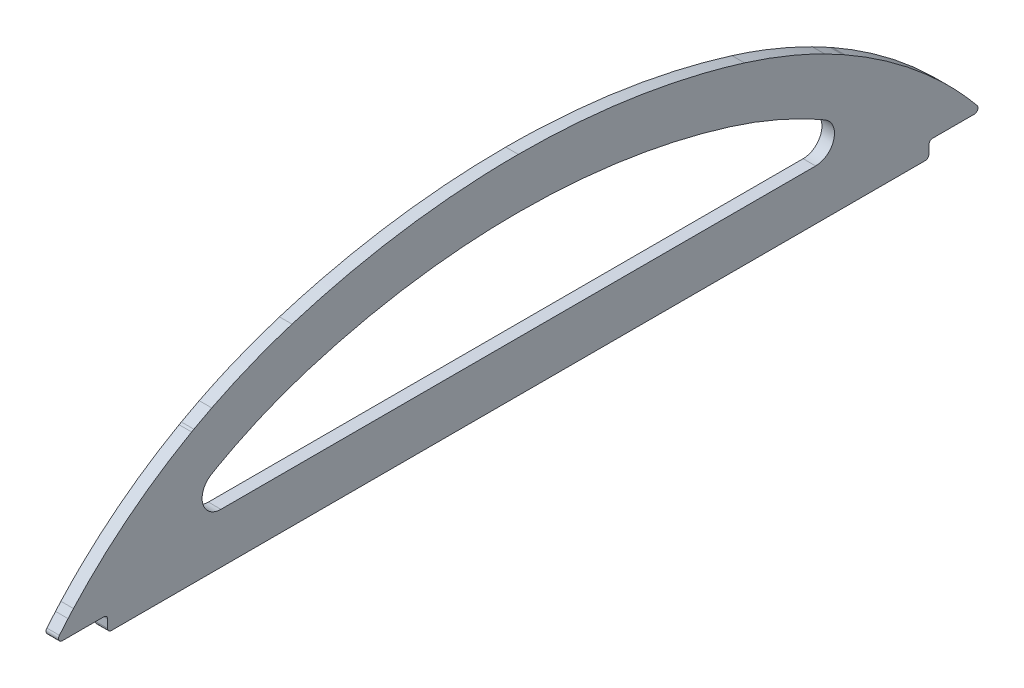
SolidWorks part; units mm, degrees
ref_plane "Front Plane" through (0, 0, 0) normal (0, 0, 1) x (1, 0, 0)
ref_plane "Top Plane" through (0, 0, 0) normal (0, 1, 0) x (1, 0, 0)
ref_plane "Right Plane" through (0, 0, 0) normal (1, 0, 0) x (0, 0, -1)
sketch "Sketch1" plane through (0, 0, 0) normal (1, 0, 0) x (0, 0, -1)
  line L0 (-96.2946, 5.9495) -> (96.2944, 5.9495)
  line L1 (-83.0866, 5.9495) -> (-83.0866, 9.1245)
  line L2 (-83.0866, 9.1245) -> (-93.8548, 9.1245)
  line L3 (83.0869, 5.9495) -> (83.0869, 9.1245)
  line L4 (83.0869, 9.1245) -> (93.8551, 9.1245)
  line L5 (72.5185, 16.1095) -> (-72.5187, 16.1095)
  spline S0 degree 3 poles (96.2944, 5.9495) (95.3162, 7.2776) (94.3159, 8.5664) (93.296, 9.8158) knots 0.775734 0.775734 0.775734 0.775734 1 1 1 1
  spline S1 degree 3 poles (93.296, 9.8158) (92.5735, 10.7008) (91.8374, 11.5701) (91.0886, 12.4237) knots 0 0 0 0 1 1 1 1
  spline S2 degree 3 poles (91.0886, 12.4237) (90.7324, 12.8297) (90.3692, 13.2365) (89.9993, 13.6442) knots 0 0 0 0 0.999999 0.999999 0.999999 0.999999
  spline S3 degree 3 poles (89.9993, 13.6442) (88.2637, 15.5574) (86.4569, 17.3838) (83.6563, 19.9929) (81.8777, 21.5829) (79.9594, 23.172) (79.0037, 23.9336) (78.8802, 24.0316) (78.8501, 24.0555) (74.7664, 27.2888) (70.4984, 30.1374) (66.0898, 32.6255) knots 0 0 0 0 0.25 0.25 0.375 0.484375 0.496094 0.496094 0.5 0.5 1 1 1 1
  spline S4 degree 3 poles (65.6328, 32.882) (64.439, 33.5479) (63.233, 34.1886) (62.0163, 34.8041) knots 0 0 0 0 0.18827 0.18827 0.18827 0.18827
  spline S5 degree 3 poles (66.0898, 32.6255) (65.9377, 32.7114) (65.7854, 32.7968) (65.6328, 32.882) knots 0 0 0 0 0.999999 0.999999 0.999999 0.999999
  spline S6 degree 3 poles (-96.2946, 5.9495) (-96.0496, 6.2797) (-95.5608, 6.9384) (-94.8141, 7.9117) (-94.0613, 8.8716) (-93.5507, 9.5017) (-93.2961, 9.8158) knots 0 0 0 0 0.252116 0.502813 0.752104 1 1 1 1
  spline S7 degree 3 poles (-93.2961, 9.8158) (-93.0545, 10.1097) (-92.5718, 10.6967) (-91.8358, 11.566) (-91.3376, 12.138) (-91.0888, 12.4237) knots 0 0 0 0 0.334016 0.667347 1 1 1 1
  spline S8 degree 3 poles (-91.0888, 12.4237) (-90.9093, 12.6273) (-90.5488, 13.0364) (-90.1831, 13.441) (-89.9995, 13.6442) knots 0 0 0 0 0.497638 1 1 1 1
  spline S9 degree 3 poles (-89.9995, 13.6442) (-89.7316, 13.9372) (-89.1963, 14.5227) (-88.3797, 15.3867) (-87.5543, 16.2391) (-86.7192, 17.0789) (-85.875, 17.9064) (-84.4559, 19.2626) (-82.7167, 20.8423) (-80.9328, 22.3643) (-79.7295, 23.3532) (-78.4521, 24.3773) (-76.7841, 25.6621) (-74.7061, 27.1763) (-72.5966, 28.6308) (-70.4569, 30.0242) (-68.2917, 31.3616) (-66.8231, 32.2047) (-66.09, 32.6255) knots 0 0 0 0 0.03885 0.077625 0.116327 0.154956 0.193513 0.232 0.347035 0.423377 0.461445 0.499444 0.583588 0.667444 0.751013 0.834295 0.917291 1 1 1 1
  spline S10 degree 3 poles (-66.09, 32.6255) (-65.9379, 32.7114) (-65.7855, 32.7968) (-65.6329, 32.882) knots 0 0 0 0 1 1 1 1
  spline S11 degree 3 poles (-65.6329, 32.882) (-65.3341, 33.0475) (-64.7366, 33.3786) (-63.8342, 33.8632) (-62.9282, 34.3396) (-62.3203, 34.6493) (-62.0164, 34.8041) knots 0 0 0 0 0.250232 0.500309 0.750231 1 1 1 1
  spline S12 degree 3 poles (-62.0164, 34.8041) (-61.1402, 35.2383) (-59.3888, 36.106) (-56.7181, 37.3111) (-54.0212, 38.445) (-51.2966, 39.499) (-48.5499, 40.4818) (-46.6986, 41.0723) (-45.7736, 41.3673) knots 0 0 0 0 0.167265 0.334295 0.501086 0.667635 0.83394 1 1 1 1
  spline S13 degree 3 poles (-45.7736, 41.3673) (-44.5402, 41.7394) (-42.0735, 42.4836) (-38.3385, 43.4787) (-34.5811, 44.385) (-30.8008, 45.1942) (-27.0006, 45.9085) (-23.1821, 46.5276) (-19.3476, 47.0516) (-15.4988, 47.4802) (-11.6376, 47.8142) (-7.7659, 48.0509) (-3.8856, 48.199) (-1.2957, 48.2167) (0, 48.2256) knots 0 0 0 0 0.083186 0.16637 0.249558 0.332759 0.415981 0.499234 0.582527 0.665873 0.749281 0.832764 0.916333 1 1 1 1
  spline S14 degree 3 poles (0, 48.2256) (1.2957, 48.2167) (3.8856, 48.199) (7.7659, 48.0509) (11.6376, 47.8142) (15.4987, 47.4802) (19.3475, 47.0516) (23.1821, 46.5276) (27.0005, 45.9085) (30.8007, 45.1941) (34.581, 44.385) (38.3384, 43.4787) (42.0734, 42.4836) (44.5401, 41.7394) (45.7734, 41.3673) knots 0 0 0 0 0.083667 0.167236 0.250719 0.334127 0.417473 0.500766 0.584019 0.667241 0.750442 0.83363 0.916814 1 1 1 1
  spline S15 degree 3 poles (45.7734, 41.3673) (46.6984, 41.0723) (48.5497, 40.4818) (51.2965, 39.499) (54.0211, 38.445) (56.718, 37.3111) (59.3887, 36.106) (61.14, 35.2383) (62.0163, 34.8041) knots 0 0 0 0 0.16606 0.332365 0.498914 0.665705 0.832735 1 1 1 1
  spline S26 degree 3 poles (-82.5005, 6.7892) (-82.2976, 7.0111) (-81.8761, 7.4722) (-81.3314, 8.054) (-80.7305, 8.6819) (-79.5477, 9.893) (-77.1002, 12.2713) (-74.3071, 14.695) (-71.6232, 16.8205) (-69.5673, 18.3671) (-67.4583, 19.8435) (-65.545, 21.1) (-64.3225, 21.8715) (-63.3625, 22.4571) (-62.6461, 22.8824) (-61.883, 23.3255) (-61.3348, 23.6402) (-61.0655, 23.7948) knots 0 0 0 0 0.03121 0.062421 0.093631 0.124842 0.249684 0.467905 0.530326 0.624209 0.749051 0.811472 0.873893 0.905103 0.936313 0.967524 0.998734 0.998734 0.998734 0.998734
  spline S27 degree 3 poles (-61.0655, 23.7948) (-61.0347, 23.8122) (-60.9732, 23.8468) (-60.8808, 23.8987) (-60.7883, 23.9505) (-60.7265, 23.9851) (-60.6956, 24.0023) knots 0.077726 0.077726 0.077726 0.077726 0.300433 0.523141 0.745848 0.968556 0.968556 0.968556 0.968556
  spline S28 degree 3 poles (-60.6956, 24.0023) (-60.5539, 24.0808) (-60.2624, 24.2422) (-59.7437, 24.5274) (-59.085, 24.8812) (-58.417, 25.2328) (-57.894, 25.5017) (-57.5985, 25.6524) (-57.4549, 25.7255) knots 0.003841 0.003841 0.003841 0.003841 0.126618 0.249395 0.494948 0.740501 0.863278 0.986054 0.986054 0.986054 0.986054
  spline S29 degree 3 poles (-57.4549, 25.7255) (-57.1384, 25.8823) (-56.4946, 26.2012) (-55.5903, 26.643) (-54.7306, 27.0521) (-53.5649, 27.5878) (-52.0522, 28.2524) (-50.2407, 29.007) (-48.4136, 29.722) (-46.8612, 30.2954) (-45.6454, 30.7221) (-44.7404, 31.0266) (-43.7827, 31.3379) (-43.0988, 31.5562) (-42.7624, 31.6635) knots 0.003251 0.003251 0.003251 0.003251 0.065263 0.127274 0.189286 0.251298 0.375321 0.499344 0.623367 0.74739 0.809401 0.871413 0.933424 0.995436 0.995436 0.995436 0.995436
  spline S30 degree 3 poles (-42.7624, 31.6635) (-42.3088, 31.8003) (-41.3911, 32.077) (-40.0755, 32.4668) (-38.8039, 32.8301) (-37.0888, 33.2976) (-34.8955, 33.8597) (-31.3915, 34.6916) (-26.9816, 35.6043) (-21.6471, 36.502) (-16.2801, 37.1998) (-11.79, 37.616) (-8.1875, 37.8477) (-5.921, 37.9544) (-4.1384, 38.0121) (-2.8096, 38.0395) (-1.4333, 38.0554) (-0.4743, 38.0621) (0, 38.0653) knots 0.001722 0.001722 0.001722 0.001722 0.032872 0.064021 0.095171 0.12632 0.188619 0.250918 0.375516 0.500113 0.624711 0.749309 0.811608 0.873907 0.905056 0.936206 0.967355 0.998505 0.998505 0.998505 0.998505
  spline S31 degree 3 poles (0, 38.0653) (0.4743, 38.0621) (1.4333, 38.0554) (2.8096, 38.0395) (4.1384, 38.0121) (5.9209, 37.9544) (8.1875, 37.8477) (11.7899, 37.616) (16.28, 37.1998) (21.6471, 36.502) (26.9815, 35.6043) (31.3914, 34.6916) (34.8954, 33.8597) (37.0887, 33.2976) (38.8037, 32.8301) (40.0754, 32.4668) (41.3909, 32.077) (42.3086, 31.8003) (42.7622, 31.6635) knots 0.001495 0.001495 0.001495 0.001495 0.032645 0.063794 0.094944 0.126093 0.188392 0.250691 0.375289 0.499887 0.624484 0.749082 0.811381 0.87368 0.90483 0.935979 0.967128 0.998278 0.998278 0.998278 0.998278
  spline S32 degree 3 poles (42.7622, 31.6635) (43.0989, 31.5561) (43.7833, 31.3376) (44.7417, 31.0261) (45.6473, 30.7213) (46.8641, 30.2943) (48.4178, 29.7204) (50.2461, 29.0048) (52.0591, 28.2494) (53.5729, 27.5841) (54.7391, 27.0481) (55.5998, 26.6384) (56.5052, 26.1958) (57.1498, 25.8766) (57.4668, 25.7195) knots 0.004564 0.004564 0.004564 0.004564 0.066624 0.128683 0.190743 0.252802 0.376922 0.501041 0.62516 0.749279 0.811339 0.873398 0.935458 0.997518 0.997518 0.997518 0.997518
  spline S33 degree 3 poles (57.4668, 25.7195) (57.7376, 25.5824) (58.2778, 25.3055) (59.0839, 24.882) (59.8859, 24.4504) (60.4176, 24.1573) (60.6828, 24.0094) knots 0.000025 0.000025 0.000025 0.000025 0.046559 0.093093 0.139626 0.18616 0.18616 0.18616 0.18616
  spline S34 degree 3 poles (60.6828, 24.0094) (60.7174, 23.9901) (60.7866, 23.9514) (60.8902, 23.8934) (60.9936, 23.8353) (61.0624, 23.7965) (61.0968, 23.7771) knots 0.001594 0.001594 0.001594 0.001594 0.250933 0.500272 0.749611 0.998951 0.998951 0.998951 0.998951
  spline S35 degree 3 poles (61.0968, 23.7771) (63.0869, 22.6538) (66.004, 20.858) (69.6507, 18.3105) (71.617, 16.8241) (72.9748, 15.7485) (73.9468, 14.9589) (75.5712, 13.5924) (78.5305, 10.9467) (80.9502, 8.4997) (82.4841, 6.8087) knots 0 0 0 0 0.249993 0.37499 0.484672 0.515921 0.562484 0.624983 0.749979 0.999972 0.999972 0.999972 0.999972
  dimension "D1" = 192.5891
  dimension "D2" = 3.175
  dimension "D3" = 13.208
  dimension "D5" = 10.16
extrude "Boss-Extrude1" add sketch "Sketch1" along normal blind 2.54 contours S15 S14 S13 S12 S11 S10 S9 S8 S7 S6 L2 L1 L0 L3 L4 S0 S1 S2 S3 S5 S4 S34 S35 L5 S26 S27 S28 S29 S30 S31 S32 S33 region at (0, 7.537, 81.1625)
fillet "Fillet1" radius 3.81 2 edges at (1.27, 16.1095, -72.5185) (1.27, 16.1095, 72.5187)
fillet "Fillet2" radius 0.762 6 edges at (1.27, 5.9495, 83.0866) (1.27, 9.1245, 83.0866) (1.27, 9.1245, -83.0869) (1.27, 5.9495, -83.0869)
